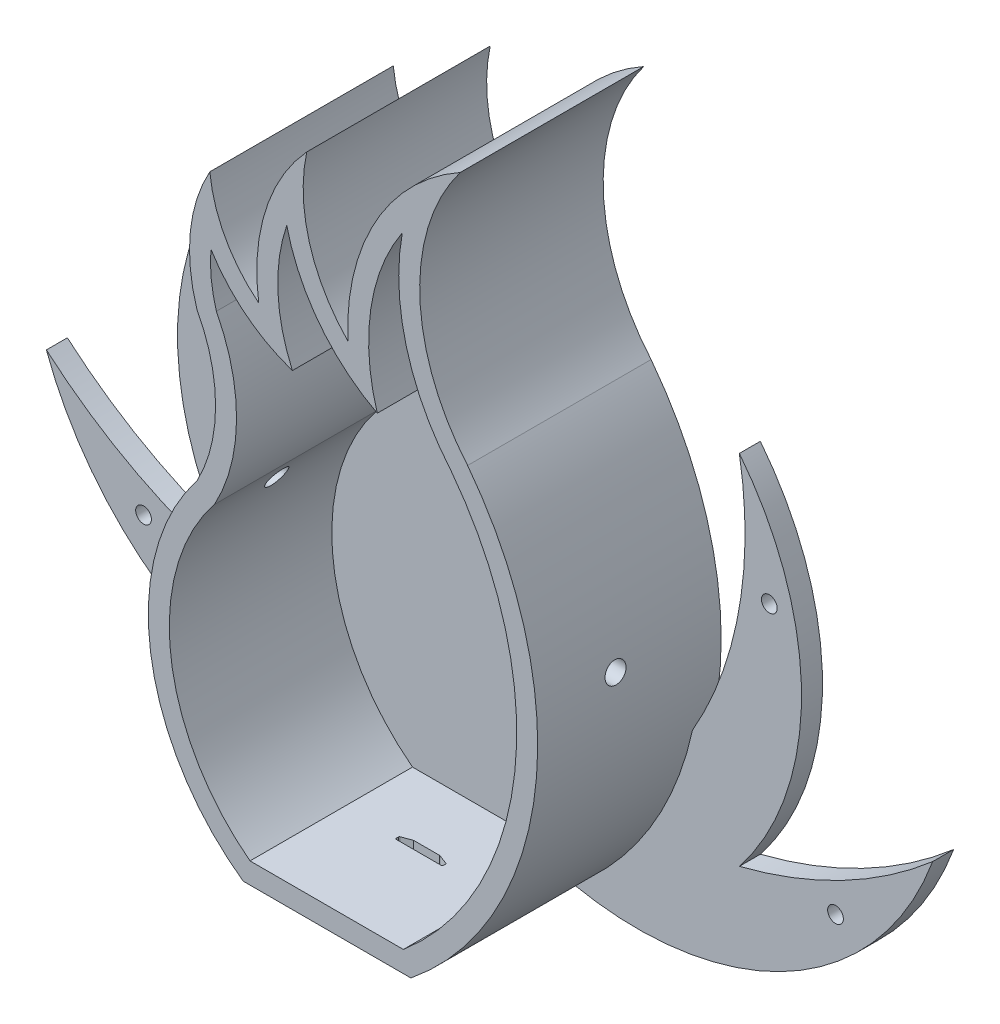
SolidWorks part; units mm, degrees
ref_plane "Plan de face" through (0, 0, 0) normal (0, 0, 1) x (1, 0, 0)
ref_plane "Plan de dessus" through (0, 0, 0) normal (0, 1, 0) x (1, 0, 0)
ref_plane "Plan de droite" through (0, 0, 0) normal (1, 0, 0) x (0, 0, -1)
sketch "Esquisse1" plane through (0, 0, 0) normal (0, 0, 1) x (1, 0, 0)
  line L0 (0, 0) -> (32, 0)
  arc A0 (32, 0) -> (42.8206, 90.0838) centre (-8.808, 50.5935) ccw
  arc A1 (42.8206, 90.0838) -> (41.4354, 137.8048) centre (71.6824, 114.8022) cw
  arc A2 (41.4354, 137.8048) -> (19.9844, 99.205) centre (61.9393, 101.1498) ccw
  arc A3 (19.9844, 99.205) -> (12.136, 126.5369) centre (41.4509, 120.1619) cw
  arc A4 (12.136, 126.5369) -> (2.9697, 97) centre (38.6019, 102.1329) ccw
  arc A5 (2.9697, 97) -> (-6.3525, 114.0145) centre (18.5156, 116.5787) cw
  arc A6 (-6.3525, 114.0145) -> (-8.8124, 90.0564) centre (19.9844, 99.205) ccw
  arc A7 (-8.8124, 90.0564) -> (-8.7976, 61.7436) centre (-35.2549, 75.8861) cw
  arc A8 (-8.7976, 61.7436) -> (0, 0) centre (24.9123, 35.0482) ccw
  point P24 (-3.4092, 104.5661)
  dimension "D3" = 65
  dimension "D4" = 38
  dimension "D5" = 42
  dimension "D6" = 30
  dimension "D7" = 36
  dimension "D9" = 25
  dimension "D10" = 43
  dimension "D11" = 30
  dimension "D1" = 32
  dimension "D8" = 24
  dimension "D12" = 99.205
  dimension "D13" = 97
extrude "Boss.-Extru.1" add sketch "Esquisse1" along normal blind 35
shell "Coque1" thickness 4 removed face at (11.1095, 81.4519, 35)
sketch "Esquisse2" plane through (0, 0, 0) normal (0, 0, 1) x (1, 0, 0)
  line L0 (-58.1664, 65) -> (112.7113, 65) construction
  line L1 (0, 0) -> (32, 0) construction
  line L2 (-59.3935, 20) -> (116.9571, 20) construction
  line L3 (32, -10.9115) -> (32, 80.3044) construction
  line L4 (16, -10.9115) -> (16, 129.2569) construction
  line L5 (32, 0) -> (32, 12.2997)
  line L6 (0, 0) -> (0, 12.2997)
  arc A0 (63.6595, 18.7727) -> (63.6595, 87) centre (20.5172, 52.8863) ccw
  arc A1 (63.6595, 87) -> (32, 12.2997) centre (-10.2516, 74.2658) cw
  arc A2 (32, 0) -> (100.5332, 38) centre (44.2318, 58.74) ccw
  arc A3 (100.5332, 38) -> (63.6595, 18.7727) centre (41.6102, 106.03) cw
  arc A4 (0, 0) -> (-68.5332, 38) centre (-12.2318, 58.74) cw
  arc A5 (-68.5332, 38) -> (-31.6595, 18.7727) centre (-9.6102, 106.03) ccw
  arc A6 (-31.6595, 18.7727) -> (-31.6595, 87) centre (11.4828, 52.8863) cw
  arc A7 (-31.6595, 87) -> (0, 12.2997) centre (42.2516, 74.2658) ccw
  circle A8 centre (69.3769, 65) radius 1.5
  circle A9 centre (82, 20) radius 1.5
  circle A10 centre (-50, 20) radius 1.5
  circle A11 centre (-37.3769, 65) radius 1.5
  dimension "D3" = 75
  dimension "D4" = 55
  dimension "D5" = 60
  dimension "D6" = 90
  dimension "D7" = 3
  dimension "D9" = 18
  dimension "D10" = 66
  dimension "D1" = 65
  dimension "D2" = 20
  dimension "D8" = 22
extrude "Boss.-Extru.2" add sketch "Esquisse2" along normal blind 4
sketch "Esquisse3" plane through (0, 0, 0) normal (1, 0, 0) x (0, 0, -1)
  line L0 (-35, 90.0838) -> (-35, 0) construction
  circle A0 centre (-20, 55) radius 2
  dimension "D2" = 4
  dimension "D3" = 15
  dimension "D1" = 55
extrude "Enlèv. mat.-Extru.1" cut sketch "Esquisse3" against normal through all both and the other way through all
sketch "Esquisse4" plane through (0, 0, 0) normal (0, -1, 0) x (1, 0, 0)
  line L0 (16, 0) -> (16, 52.9944) construction
  line L1 (0, 0) -> (32, 0) construction
  line L2 (13.5363, 16) -> (18.4637, 16)
  line L3 (18.534, 16.0127) -> (20.3702, 16.7013)
  line L4 (20.5, 16.8886) -> (20.5, 17.3)
  line L5 (20.3, 17.5) -> (11.7, 17.5)
  line L6 (0, 4) -> (-68.5332, 4) construction
  line L7 (13.5363, 16) -> (11.6298, 16.7013)
  line L8 (11.5, 16.8886) -> (11.5, 17.3)
  arc A0 (18.4637, 16) -> (18.534, 16.0127) centre (18.4637, 16.2) ccw
  arc A1 (20.3702, 16.7013) -> (20.5, 16.8886) centre (20.3, 16.8886) ccw
  arc A2 (20.5, 17.3) -> (20.3, 17.5) centre (20.3, 17.3) ccw
  arc A3 (11.6298, 16.7013) -> (11.5, 16.8886) centre (11.7, 16.8886) cw
  arc A4 (11.5, 17.3) -> (11.7, 17.5) centre (11.7, 17.3) cw
  point P15 (18.5, 16)
  point P18 (20.5, 16.75)
  point P21 (20.5, 17.5)
  point P23 (16, 16)
  point P30 (16, 17.5)
  dimension "D6" = 0.2
  dimension "D1" = 12
  dimension "D2" = 2.5
  dimension "D3" = 4.5
  dimension "D4" = 0.75
  dimension "D5" = 1.5
extrude "Enlèv. mat.-Extru.3" cut sketch "Esquisse4" against normal up to next
